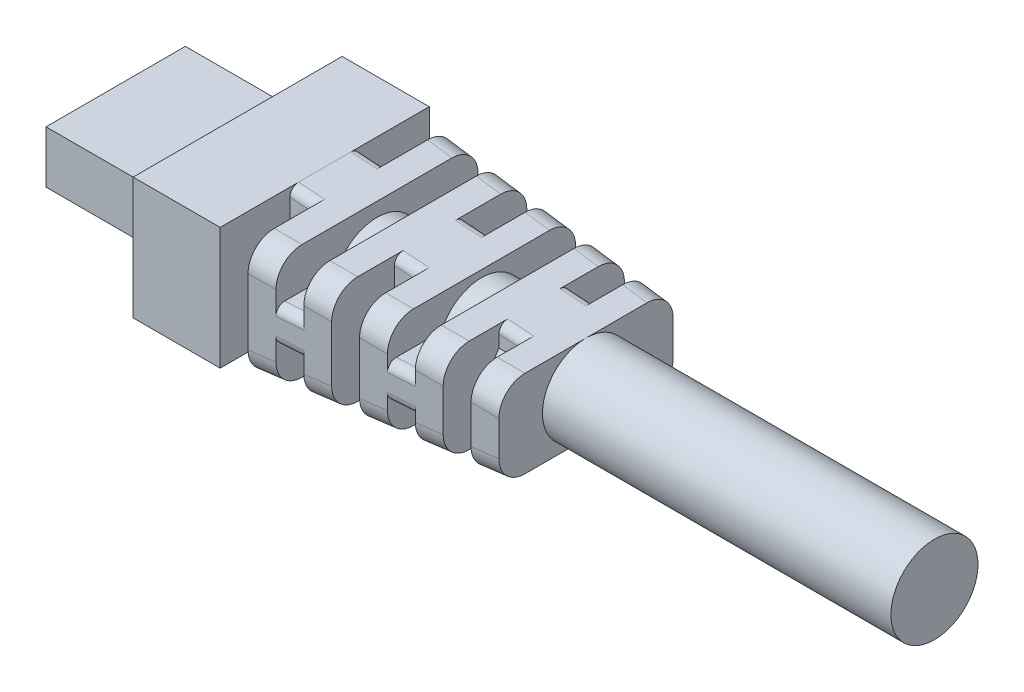
SolidWorks part; units mm, degrees
ref_plane "Спереди" through (0, 0, 0) normal (0, 0, 1) x (1, 0, 0)
ref_plane "Сверху" through (0, 0, 0) normal (0, 1, 0) x (1, 0, 0)
ref_plane "Справа" through (0, 0, 0) normal (1, 0, 0) x (0, 0, -1)
sketch "Эскиз1" plane through (0, 0, 0) normal (0, 0, 1) x (1, 0, 0)
  line L1 (0, 0) -> (7, 0)
  line L2 (0, 0) -> (0, 3)
  line L3 (0, 3) -> (7, 3)
  line L4 (7, 0) -> (7, 3)
  dimension "D1" = 7
  dimension "D2" = 3
extrude "Бобышка-Вытянуть1" add sketch "Эскиз1" along normal blind 8
sketch "Эскиз2" plane through (7, 0, 0) normal (1, 0, 0) x (0, 0, -1)
  line L0 (-8, 0) -> (0, 0) construction
  line L1 (-10, -2) -> (2, -2)
  line L2 (-10, -2) -> (-10, 5)
  line L3 (-10, 5) -> (2, 5)
  line L4 (2, -2) -> (2, 5)
  line L5 (0, 0) -> (0, 3) construction
  line L6 (-8, 0) -> (-8, 3) construction
  line L7 (-8, 3) -> (0, 3) construction
  point P10 (-4, 3)
  dimension "D1" = 2
  dimension "D2" = 2
  dimension "D3" = 2
  dimension "D4" = 2
extrude "Бобышка-Вытянуть2" add sketch "Эскиз2" along normal blind 20
chamfer "Фаска1" distance 15 distance2 1 4 edges at (27, 5, 4) (27, 1.5, 10) (27, -2, 4) (27, 1.5, -2) first distance on face at (17, 5, 4) first distance on face at (17, 1.5, 10) first distance on face at (17, -2, 4) first distance on face at (17, 1.5, -2)
ref_plane "Плоскость1" through (0, 0, 4) normal (0, 0, 1) x (1, 0, 0)
sketch "Эскиз4" plane through (0, 0, -2) normal (0, 0, -1) x (-1, 0, 0)
  line L0 (-25.5, 4.9865) -> (-24, 4.9865)
  line L1 (-25.5, 4.9865) -> (-25.5, 2.4865)
  line L2 (-25.5, 2.4865) -> (-24, 2.4865)
  line L3 (-24, 4.9865) -> (-24, 2.4865)
  line L4 (-22.5, 4.9865) -> (-21, 4.9865)
  line L5 (-22.5, 4.9865) -> (-22.5, 2.4865)
  line L6 (-22.5, 2.4865) -> (-21, 2.4865)
  line L7 (-21, 4.9865) -> (-21, 2.4865)
  line L8 (-19.5, 4.9865) -> (-18, 4.9865)
  line L9 (-19.5, 4.9865) -> (-19.5, 2.4865)
  line L10 (-19.5, 2.4865) -> (-18, 2.4865)
  line L11 (-18, 4.9865) -> (-18, 2.4865)
  line L12 (-16.5, 4.9865) -> (-15, 4.9865)
  line L13 (-16.5, 4.9865) -> (-16.5, 2.4865)
  line L14 (-16.5, 2.4865) -> (-15, 2.4865)
  line L15 (-15, 4.9865) -> (-15, 2.4865)
  line L16 (-12, 5) -> (-7, 5) construction
  line L17 (-13.5, 5) -> (-13.5, 2.4865)
  line L18 (-13.5, 2.4865) -> (-12, 2.4865)
  line L19 (-12, 5) -> (-12, 2.4865)
  line L20 (-22.5, 0.4865) -> (-21, 0.4865)
  line L21 (-22.5, 0.4865) -> (-22.5, -2.0135)
  line L22 (-22.5, -2.0135) -> (-21, -2.0135)
  line L23 (-21, 0.4865) -> (-21, -2.0135)
  line L24 (-19.5, 0.4865) -> (-18, 0.4865)
  line L25 (-19.5, 0.4865) -> (-19.5, -2.0135)
  line L26 (-19.5, -2.0135) -> (-18, -2.0135)
  line L27 (-18, 0.4865) -> (-18, -2.0135)
  line L28 (-16.5, 0.4865) -> (-15, 0.4865)
  line L29 (-16.5, 0.4865) -> (-16.5, -2.0135)
  line L30 (-16.5, -2.0135) -> (-15, -2.0135)
  line L31 (-15, 0.4865) -> (-15, -2.0135)
  line L32 (-13.5, 0.4865) -> (-12, 0.4865)
  line L33 (-13.5, 0.4865) -> (-13.5, -2)
  line L34 (-13.5, -2) -> (-12, -2)
  line L35 (-12, 0.4865) -> (-12, -2)
  line L36 (-25.5, 0.4865) -> (-24, 0.4865)
  line L37 (-25.5, 0.4865) -> (-25.5, -2.0135)
  line L38 (-25.5, -2.0135) -> (-24, -2.0135)
  line L39 (-24, 0.4865) -> (-24, -2.0135)
  line L40 (-12, 5) -> (-12, -2) construction
  line L41 (-13.5, 5) -> (-12, 5)
  dimension "D1" = 1.5
  dimension "D2" = 2.5
extrude "Вырез-Вытянуть1" cut sketch "Эскиз4" against normal blind 4
mirror "Зеркальное отражение1" about plane through (0, 0, 4) normal (0, 0, 1) of "Вырез-Вытянуть1"
fillet "Скругление1" radius 1.5 20 edges at (26.25, 4.05, 9.05) (23.25, 4.25, 9.25) (20.25, 4.45, 9.45) (17.25, 4.65, 9.65) (14.25, 4.85, 9.85) (26.25, -1.05, 9.05) (23.25, -1.25, 9.25) (20.25, -1.45, 9.45) (17.25, -1.65, 9.65) (14.25, -1.85, 9.85) (26.25, -1.05, -1.05) (23.25, -1.25, -1.25) (20.25, -1.45, -1.45) (17.25, -1.65, -1.65) (14.25, -1.85, -1.85) (26.25, 4.05, -1.05) (23.25, 4.25, -1.25) (20.25, 4.45, -1.45) (17.25, 4.65, -1.65) (14.25, 4.85, -1.85)
sketch "Эскиз9" plane through (0, 0, 10) normal (0, 0, 1) x (1, 0, 0)
  line L1 (12, 0.4865) -> (13.5, 0.4865)
  line L2 (12, 0.4865) -> (12, 2.4865)
  line L3 (12, 2.4865) -> (13.5, 2.4865)
  line L4 (13.5, 0.4865) -> (13.5, 2.4865)
  line L5 (18, 0.4865) -> (19.5, 0.4865)
  line L6 (18, 0.4865) -> (18, 2.4865)
  line L7 (18, 2.4865) -> (19.5, 2.4865)
  line L8 (19.5, 0.4865) -> (19.5, 2.4865)
  line L9 (24, 0.4865) -> (25.5, 0.4865)
  line L10 (24, 0.4865) -> (24, 2.4865)
  line L11 (24, 2.4865) -> (25.5, 2.4865)
  line L12 (25.5, 0.4865) -> (25.5, 2.4865)
extrude "Вырез-Вытянуть3" cut sketch "Эскиз9" against normal blind 4
mirror "Зеркальное отражение2" about plane through (0, 0, 4) normal (0, 0, 1) of "Вырез-Вытянуть3"
ref_plane "Плоскость2" through (0, 1.5, 0) normal (0, 1, 0) x (1, 0, 0)
sketch "Эскиз10" plane through (0, 5, 0) normal (0, 1, 0) x (1, 0, 0)
  line L1 (15, -6) -> (16.5, -6)
  line L2 (15, -6) -> (15, -2)
  line L3 (15, -2) -> (16.5, -2)
  line L4 (16.5, -6) -> (16.5, -2)
  line L5 (21, -6) -> (22.5, -6)
  line L6 (21, -6) -> (21, -2)
  line L7 (21, -2) -> (22.5, -2)
  line L8 (22.5, -6) -> (22.5, -2)
extrude "Вырез-Вытянуть4" cut sketch "Эскиз10" against normal blind 2.5
mirror "Зеркальное отражение3" about plane through (0, 1.5, 0) normal (0, 1, 0) of "Вырез-Вытянуть4"
sketch "Эскиз11" plane through (27, 0, 0) normal (1, 0, 0) x (0, 0, -1)
  line L0 (-4, 3.3) -> (-4, -3.3) construction
  line L1 (6.05, 1.5) -> (-6.05, 1.5) construction
  circle A0 centre (-4, 1.5) radius 2.5
extrude "Бобышка-Вытянуть3" add sketch "Эскиз11" against normal blind 20 and the other way blind 20
fillet "Скругление2" radius 0.5 6 edges at (24.75, -1.15, 6) (24.75, -1.15, 2) (18.75, -1.55, 6) (18.75, -1.55, 2) (12.75, -1.95, 6) (12.75, -1.95, 2)
fillet "Скругление3" radius 0.5 4 edges at (21.75, 2.4865, 9.35) (21.75, 0.4865, 9.35) (15.75, 2.4865, 9.75) (15.75, 0.4865, 9.75)
fillet "Скругление4" radius 0.5 6 edges at (24.75, 4.15, 2) (24.75, 4.15, 6) (18.75, 4.55, 2) (18.75, 4.55, 6) (12.75, 4.95, 2) (12.75, 4.95, 6)
fillet "Скругление5" radius 0.5 4 edges at (21.75, 0.4865, -1.35) (21.75, 2.4865, -1.35) (15.75, 2.4865, -1.75) (15.75, 0.4865, -1.75)
